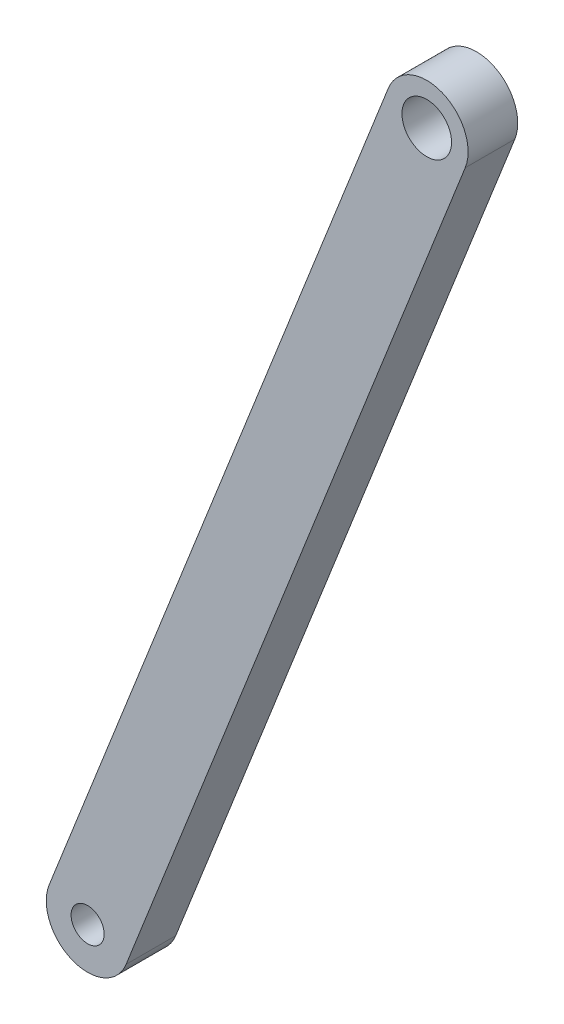
SolidWorks part; units mm, degrees
ref_plane "Ebene vorne" through (0, 0, 0) normal (0, 0, 1) x (1, 0, 0)
ref_plane "Ebene oben" through (0, 0, 0) normal (0, 1, 0) x (1, 0, 0)
ref_plane "Ebene rechts" through (0, 0, 0) normal (1, 0, 0) x (0, 0, -1)
sketch "Skizze1" plane through (0, 0, 0) normal (0, 0, 1) x (1, 0, 0)
  line L1 (-11.6, 588.1) -> (34, 588.1)
  line L2 (-11.6, 588.1) -> (-11.6, 564.1)
  line L3 (-11.6, 564.1) -> (34, 564.1)
  line L4 (34, 588.1) -> (34, 564.1)
  circle A0 centre (29, 576.1) radius 2
  point P6 (-11.6, 576.1)
sketch "Skizze2" plane through (0, 0, 0) normal (0, 0, 1) x (1, 0, 0)
  circle A0 centre (0, 680) radius 3.25
  circle A1 centre (70, 680) radius 3.25
sketch "Skizze3" plane through (0, 0, 0) normal (0, 0, 1) x (1, 0, 0)
  line L0 (24.349, 577.9353) -> (65.349, 681.8353)
  line L1 (33.651, 574.2647) -> (74.651, 678.1647)
  circle A0 centre (70, 680) radius 3
  circle A1 centre (29, 576.1) radius 2
  arc A2 (24.349, 577.9353) -> (33.651, 574.2647) centre (29, 576.1) ccw
  arc A3 (74.651, 678.1647) -> (65.349, 681.8353) centre (70, 680) ccw
  point P6 (0, 0)
  dimension "D1" = 10
  dimension "D2" = 6
extrude "Aufsatz-Linear austragen1" add sketch "Skizze3" along normal blind 3 and the other way blind 3
